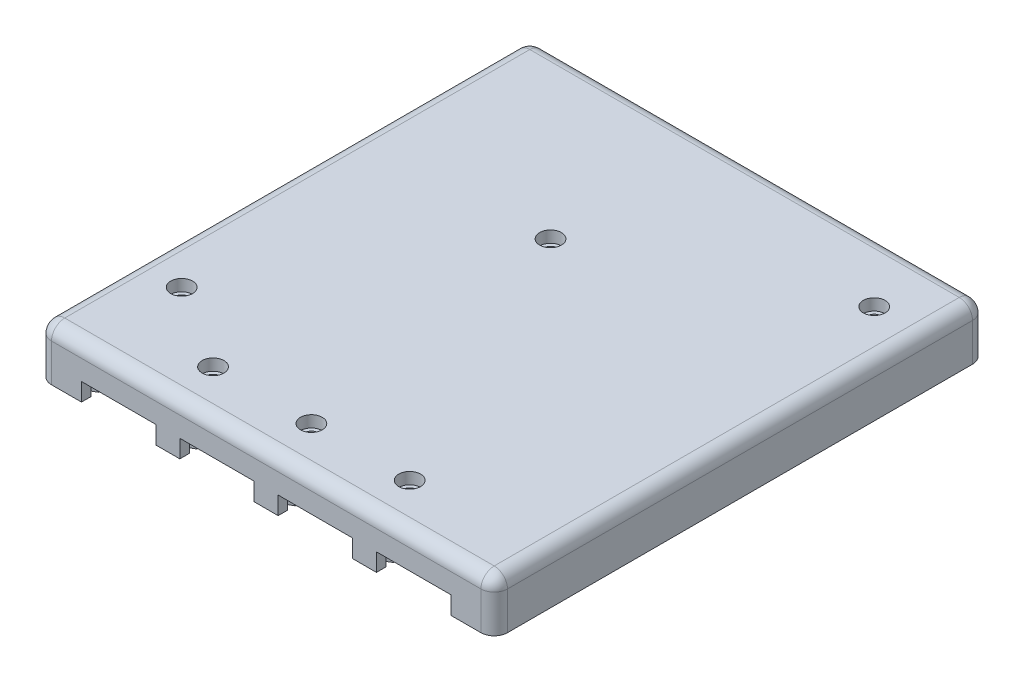
SolidWorks part; units mm, degrees
ref_plane "Front Plane" through (0, 0, 0) normal (0, 0, 1) x (1, 0, 0)
ref_plane "Top Plane" through (0, 0, 0) normal (0, 1, 0) x (1, 0, 0)
ref_plane "Right Plane" through (0, 0, 0) normal (1, 0, 0) x (0, 0, -1)
sketch "Sketch1" plane through (0, 0, 0) normal (0, 1, 0) x (1, 0, 0)
  line L0 (-1, -1) -> (-1, 15.7637) construction
  line L1 (-6, -6) -> (79.8, -6)
  line L2 (-6, -6) -> (-6, 86.5)
  line L3 (-6, 86.5) -> (79.8, 86.5)
  line L4 (79.8, -6) -> (79.8, 86.5)
  line L5 (-1, -1) -> (16.6536, -1) construction
  circle A0 centre (2.5, 12.5) radius 2.05
  circle A1 centre (18.4, 2.5) radius 2.05
  circle A2 centre (36.9, 2.5) radius 2.05
  circle A3 centre (55.4, 2.5) radius 2.05
  circle A4 centre (29.3, 55.1) radius 2.05
  circle A5 centre (70.8, 74.5) radius 2.05
  dimension "D16" = 4.1
  dimension "D1" = 92.5
  dimension "D2" = 85.8
  dimension "D3" = 5
  dimension "D4" = 1
  dimension "D5" = 1
  dimension "D6" = 5
  dimension "D7" = 12.5
  dimension "D8" = 2.5
  dimension "D9" = 18.4
  dimension "D10" = 18.5
  dimension "D11" = 18.5
  dimension "D12" = 55.1
  dimension "D13" = 29.3
  dimension "D14" = 41.5
  dimension "D15" = 74.5
  dimension "D17" = 2.5
extrude "Boss-Extrude1" add sketch "Sketch1" along normal blind 3.175
sketch "Sketch2" plane through (0, 0, 0) normal (0, 1, 0) x (1, 0, 0)
  line L0 (2.5, 7.5) -> (-1, 7.5)
  line L1 (-6, 86.5) -> (79.8, 86.5)
  line L2 (-6, 86.5) -> (-6, -6)
  line L3 (-6, -6) -> (79.8, -6)
  line L4 (79.8, 86.5) -> (79.8, -6)
  line L5 (-1, 7.5) -> (-1, -1)
  line L6 (-1, -1) -> (13.4, -1)
  line L7 (13.4, -1) -> (13.4, 2.5)
  line L8 (2.5, 17.5) -> (-1, 17.5)
  line L9 (-1, 17.5) -> (-1, 81.5)
  line L10 (-1, 81.5) -> (65.8, 81.5)
  line L11 (65.8, 74.5) -> (65.8, 81.5)
  line L13 (70.8, 69.5) -> (74.8, 69.5)
  line L14 (74.8, 69.5) -> (74.8, -1)
  line L15 (74.8, -1) -> (60.4, -1)
  line L16 (60.4, -1) -> (60.4, 2.5)
  line L17 (23.4, 2.5) -> (23.4, -1)
  line L18 (23.4, -1) -> (31.9, -1)
  line L19 (31.9, -1) -> (31.9, 2.5)
  line L20 (41.9, 2.5) -> (41.9, -1)
  line L21 (41.9, -1) -> (50.4, -1)
  line L22 (50.4, -1) -> (50.4, 2.5)
  circle A0 centre (2.5, 12.5) radius 1.35
  circle A1 centre (18.4, 2.5) radius 1.35
  circle A2 centre (36.9, 2.5) radius 1.35
  circle A3 centre (55.4, 2.5) radius 1.35
  circle A4 centre (29.3, 55.1) radius 1.35
  circle A5 centre (70.8, 74.5) radius 1.35
  circle A6 centre (29.3, 55.1) radius 3.35
  arc A7 (2.5, 17.5) -> (2.5, 7.5) centre (2.5, 12.5) cw
  arc A8 (13.4, 2.5) -> (23.4, 2.5) centre (18.4, 2.5) cw
  arc A9 (31.9, 2.5) -> (41.9, 2.5) centre (36.9, 2.5) cw
  arc A10 (50.4, 2.5) -> (60.4, 2.5) centre (55.4, 2.5) cw
  arc A11 (65.8, 74.5) -> (70.8, 69.5) centre (70.8, 74.5) ccw
  dimension "D1" = 2.7
  dimension "D2" = 6.7
  dimension "D3" = 5
  dimension "D4" = 5
  dimension "D5" = 5
  dimension "D6" = 5
  dimension "D7" = 5
extrude "Boss-Extrude2" add sketch "Sketch2" against normal blind 1.905 contours L4 L1 L2 L3 A0 A1 A2 A3 A5 L11 A11 L13 L14 L15 L16 A10 L22 L21 L20 A9 L19 L18 L17 A8 L7 L6 L5 L0 A7 L8 L9 L10 | A6 A4 region at (36.9, 0, -85.2383) region at (26.0448, 0, -55.1)
extrude "Boss-Extrude3" add sketch "Sketch2<3>" along normal blind 1 contours L4 L1 L2 L3 A0 A1 A2 A3 A5 L11 A11 L13 L14 L15 L16 A10 L22 L21 L20 A9 L19 L18 L17 A8 L7 L6 L5 L0 A7 L8 L9 L10 | A6 A4 region at (36.9, 0, -85.2383) region at (26.0448, 0, -55.1)
sketch "Sketch2<3>" plane through (0, 0, 0) normal (0, 1, 0) x (1, 0, 0) same geometry as "Sketch2"
ref_plane "Plane1" through (0, -1.905, 0) normal (0, -1, 0) x (-1, 0, 0)
sketch "Sketch3" plane through (0, -1.905, 0) normal (0, -1, 0) x (-1, 0, 0)
  line L1 (6, 86.5) -> (-79.8, 86.5)
  line L2 (6, 86.5) -> (6, -6)
  line L3 (6, -6) -> (-79.8, -6)
  line L4 (-79.8, 86.5) -> (-79.8, -6)
  line L5 (1, 81.5) -> (-74.8, 81.5)
  line L6 (1, 81.5) -> (1, -1)
  line L7 (1, -1) -> (-74.8, -1)
  line L8 (-74.8, 81.5) -> (-74.8, -1)
  dimension "D1" = 5
  dimension "D2" = 5
  dimension "D3" = 5
  dimension "D4" = 5
extrude "Boss-Extrude4" add sketch "Sketch3" along normal blind 4.55
sketch "Sketch4" plane through (0, 0, 0) normal (0, 0, 1) x (1, 0, 0)
  line L0 (79.8, -6.455) -> (-6, -6.455) construction
  line L1 (2.15, -3.095) -> (16.15, -3.095)
  line L2 (2.15, -3.095) -> (2.15, -9.845)
  line L3 (2.15, -9.845) -> (16.15, -9.845)
  line L4 (16.15, -3.095) -> (16.15, -9.845)
  line L5 (20.65, -3.095) -> (34.65, -3.095)
  line L6 (20.65, -3.095) -> (20.65, -9.845)
  line L7 (20.65, -9.845) -> (34.65, -9.845)
  line L8 (34.65, -3.095) -> (34.65, -9.845)
  line L9 (39.15, -3.095) -> (53.15, -3.095)
  line L10 (39.15, -3.095) -> (39.15, -9.845)
  line L11 (39.15, -9.845) -> (53.15, -9.845)
  line L12 (53.15, -3.095) -> (53.15, -9.845)
  line L13 (57.65, -3.095) -> (71.65, -3.095)
  line L14 (57.65, -3.095) -> (57.65, -9.845)
  line L15 (57.65, -9.845) -> (71.65, -9.845)
  line L16 (71.65, -3.095) -> (71.65, -9.845)
  point P16 (9.15, -3.095)
  point P17 (27.65, -3.095)
  point P18 (46.15, -3.095)
  point P19 (64.65, -3.095)
  dimension "D1" = 14
  dimension "D2" = 14
  dimension "D3" = 14
  dimension "D4" = 14
  dimension "D5" = 9.15
  dimension "D6" = 18.5
  dimension "D7" = 18.5
  dimension "D8" = 18.5
  dimension "D9" = 6.75
  dimension "D10" = 3.36
extrude "Cut-Extrude1" cut sketch "Sketch4" along normal through all
sketch "Sketch5" plane through (0, 0, 0) normal (0, 0, 1) x (1, 0, 0)
  line L0 (-1, -6.455) -> (74.8, -6.455) construction
  line L1 (53, -4.455) -> (63, -4.455)
  line L2 (53, -4.455) -> (53, -10.455)
  line L3 (53, -10.455) -> (63, -10.455)
  line L4 (63, -4.455) -> (63, -10.455)
  point P4 (58, -4.455)
  dimension "D1" = 58
  dimension "D2" = 10
  dimension "D3" = 6
  dimension "D4" = 2
extrude "Cut-Extrude2" cut sketch "Sketch5" against normal through all
ref_plane "Plane2" through (-6, 0, 0) normal (-1, 0, 0) x (0, 0, 1)
sketch "Sketch6" plane through (-6, 0, 0) normal (-1, 0, 0) x (0, 0, 1)
  line L0 (-59.6, 0) -> (-59.6, -8.95)
  line L1 (-59.6, 0) -> (-50.6, 0)
  line L2 (-59.6, -8.95) -> (-59.1311, -8.95)
  line L3 (-50.6, 0) -> (-50.6, -8.95)
  line L4 (-50.6, -8.95) -> (-51.0689, -8.95)
  arc A0 (-59.1311, -8.95) -> (-51.0689, -8.95) centre (-55.1, -10.95) cw
  point P3 (-55.1, 0)
  dimension "D1" = 4.5
  dimension "D2" = 10.95
  dimension "D3" = 55.1
  dimension "D4" = 9
  dimension "D5" = 2
extrude "Boss-Extrude5" add sketch "Sketch6" against normal blind 3.5
fillet "Fillet1" radius 2.5 1 edges at (79.8, -1.64, 6)
fillet "Fillet2" radius 2.5 1 edges at (79.8, -1.64, -86.5)
fillet "Fillet3" radius 2.5 1 edges at (-6, -1.64, -86.5)
fillet "Fillet4" radius 2.5 1 edges at (-6, -1.64, 6)
fillet "Fillet5" radius 2.5 8 edges at (79.0678, 3.175, -85.7678) (79.8, 3.175, -40.25) (79.0678, 3.175, 5.2678) (36.9, 3.175, 6) (-5.2678, 3.175, 5.2678) (-6, 3.175, -40.25) (-5.2678, 3.175, -85.7678) (36.9, 3.175, -86.5)
ref_plane "Plane3" through (0, -6.455, 0) normal (0, -1, 0) x (-1, 0, 0)
sketch "Sketch7" plane through (0, -6.455, 0) normal (0, -1, 0) x (-1, 0, 0)
  line L0 (-2.15, -3.5) -> (-0.9, -3.5) construction
  line L1 (-2.15, -6) -> (-2.15, -1) construction
  line L2 (-2.15, -2.8) -> (-0.9, -3.5)
  line L3 (-2.15, -6) -> (-2.15, -1) construction
  line L4 (-0.9, -3.5) -> (-2.15, -4.2)
  line L5 (-2.15, -4.2) -> (-2.15, -2.8)
  line L6 (-16.15, -2.8) -> (-17.4, -3.5)
  line L7 (-16.15, -1) -> (-16.15, -6) construction
  line L8 (-17.4, -3.5) -> (-16.15, -4.2)
  line L9 (-16.15, -4.2) -> (-16.15, -2.8)
  line L10 (-20.65, -2.8) -> (-19.4, -3.5)
  line L11 (-20.65, -6) -> (-20.65, -1) construction
  line L12 (-19.4, -3.5) -> (-20.65, -4.2)
  line L13 (-20.65, -6) -> (-20.65, -1) construction
  line L14 (-20.65, -4.2) -> (-20.65, -2.8)
  line L15 (-34.65, -2.8) -> (-35.9, -3.5)
  line L16 (-34.65, -6) -> (-34.65, -1) construction
  line L17 (-35.9, -3.5) -> (-34.65, -4.2)
  line L18 (-34.65, -1) -> (-34.65, -6) construction
  line L19 (-34.65, -4.2) -> (-34.65, -2.8)
  line L20 (-39.15, -2.8) -> (-39.15, -4.2)
  line L21 (-39.15, -6) -> (-39.15, -1) construction
  line L22 (-39.15, -4.2) -> (-37.9, -3.5)
  line L23 (-37.9, -3.5) -> (-39.15, -2.8)
  line L24 (-53.15, -2.8) -> (-53.15, -4.2)
  line L25 (-53.15, -1) -> (-53.15, -6) construction
  line L26 (-53.15, -4.2) -> (-54.4, -3.5)
  line L27 (-54.4, -3.5) -> (-53.15, -2.8)
  line L28 (-57.65, -4.2) -> (-56.4, -3.5)
  line L29 (-57.65, -6) -> (-57.65, -1) construction
  line L30 (-56.4, -3.5) -> (-57.65, -2.8)
  line L31 (-57.65, -2.8) -> (-57.65, -4.2)
  line L32 (-71.65, -2.8) -> (-72.9, -3.5)
  line L33 (-71.65, -6) -> (-71.65, -1) construction
  line L34 (-72.9, -3.5) -> (-71.65, -4.2)
  line L35 (-71.65, -4.2) -> (-71.65, -2.8)
  dimension "D1" = 1.25
  dimension "D2" = 1.4
  dimension "D3" = 1.25
  dimension "D4" = 1.25
  dimension "D5" = 1.25
  dimension "D6" = 1.25
  dimension "D7" = 1.25
  dimension "D8" = 1.25
  dimension "D9" = 1.25
extrude "Cut-Extrude3" cut sketch "Sketch7" against normal blind 3.36
sketch "Sketch8" plane through (0, 0, 0) normal (1, 0, 0) x (0, 0, -1)
  line L0 (-4.2, -3.15) -> (-2.8, -3.15)
  line L1 (-2.8, -3.15) -> (-3.5, -1.85)
  line L2 (-3.5, -1.85) -> (-4.2, -3.15)
  line L3 (-3.5, -3.15) -> (-3.5, -1.85) construction
  dimension "D1" = 1.3
  dimension "D2" = 1.4
  dimension "D3" = 3.15
  dimension "D4" = 3.5
extrude "Cut-Extrude4" cut sketch "Sketch8" along normal blind 75
ref_plane "Plane4" through (0, 0, 6) normal (0, 0, 1) x (1, 0, 0)
sketch "Sketch10" plane through (0, 0, 6) normal (0, 0, 1) x (1, 0, 0)
  line L1 (2.15, -3.095) -> (-2.351, -3.095)
  line L2 (2.15, -3.095) -> (2.15, -0.095)
  line L3 (2.15, -0.095) -> (-2.351, -0.095)
  line L4 (-2.351, -3.095) -> (-2.351, -0.095)
  line L5 (20.65, -3.095) -> (16.149, -3.095)
  line L6 (20.65, -3.095) -> (20.65, -0.095)
  line L7 (20.65, -0.095) -> (16.149, -0.095)
  line L8 (16.149, -3.095) -> (16.149, -0.095)
  line L9 (39.15, -3.095) -> (34.649, -3.095)
  line L10 (39.15, -3.095) -> (39.15, -0.095)
  line L11 (39.15, -0.095) -> (34.649, -0.095)
  line L12 (34.649, -3.095) -> (34.649, -0.095)
  line L13 (57.65, -3.095) -> (53.149, -3.095)
  line L14 (57.65, -3.095) -> (57.65, -0.095)
  line L15 (57.65, -0.095) -> (53.149, -0.095)
  line L16 (53.149, -3.095) -> (53.149, -0.095)
  line L17 (71.65, -3.095) -> (76.151, -3.095)
  line L18 (71.65, -3.095) -> (71.65, -0.095)
  line L19 (71.65, -0.095) -> (76.151, -0.095)
  line L20 (76.151, -3.095) -> (76.151, -0.095)
  dimension "D1" = 3
  dimension "D2" = 4.501
extrude "Boss-Extrude6" add sketch "Sketch10" against normal blind 5
